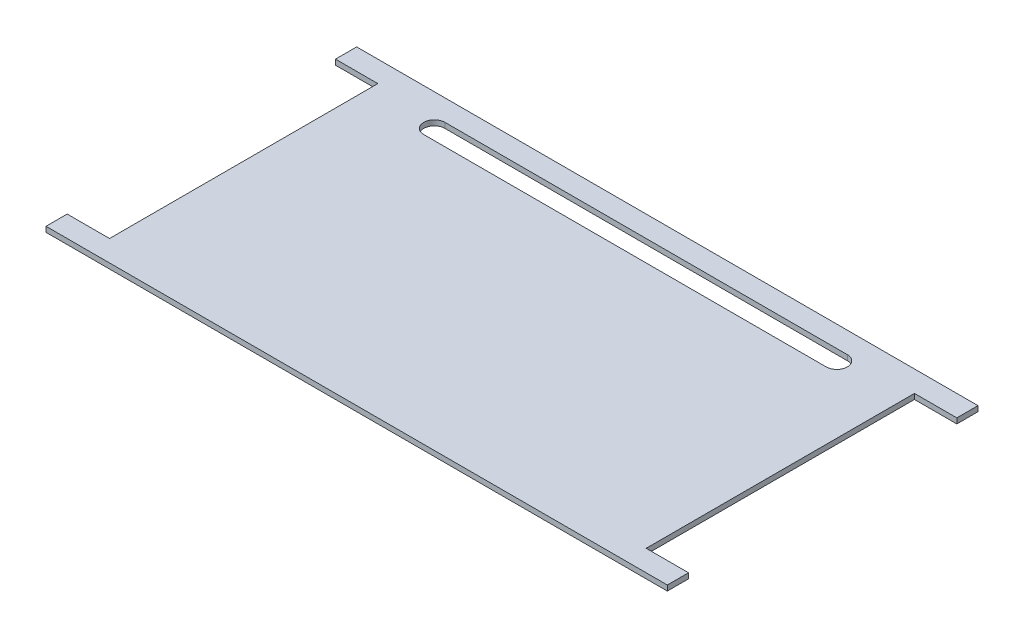
SolidWorks part; units mm, degrees
material "Maple"
ref_plane "Front Plane" through (0, 0, 0) normal (0, 0, 1) x (1, 0, 0)
ref_plane "Top Plane" through (0, 0, 0) normal (0, 1, 0) x (1, 0, 0)
ref_plane "Right Plane" through (0, 0, 0) normal (1, 0, 0) x (0, 0, -1)
sketch "Sketch1" plane through (0, 0, 0) normal (0, 1, 0) x (1, 0, 0)
  line L1 (-279.4, -139.7) -> (279.4, -139.7)
  line L2 (-279.4, -139.7) -> (-279.4, 139.7)
  line L3 (-279.4, 139.7) -> (279.4, 139.7)
  line L4 (279.4, -139.7) -> (279.4, 139.7)
  line L5 (-279.4, -139.7) -> (279.4, 139.7) construction
  line L6 (-279.4, 139.7) -> (279.4, -139.7) construction
  point P0 (0, 0)
  dimension "D1" = 279.4
  dimension "D2" = 558.8
extrude "Boss-Extrude1" add sketch "Sketch1" along normal mid plane 4.7625 contours L3 L4 L1 L2
sketch "Sketch2" plane through (0, 2.3813, 0) normal (0, 1, 0) x (1, 0, 0)
  line L0 (-279.4, -139.7) -> (-279.4, 139.7) construction
  line L1 (-279.4, 120.65) -> (-241.3, 120.65)
  line L2 (-279.4, 120.65) -> (-279.4, -120.65)
  line L3 (-279.4, -120.65) -> (-241.3, -120.65)
  line L4 (-241.3, 120.65) -> (-241.3, -120.65)
  line L5 (279.4, -139.7) -> (279.4, 139.7) construction
  line L6 (279.4, 120.65) -> (241.3, 120.65)
  line L7 (279.4, 120.65) -> (279.4, -120.65)
  line L8 (279.4, -120.65) -> (241.3, -120.65)
  line L9 (241.3, 120.65) -> (241.3, -120.65)
  line L10 (-241.3, 0) -> (241.3, 0) construction
  line L11 (-279.4, -139.7) -> (279.4, -139.7) construction
  dimension "D1" = 38.1
  dimension "D2" = 19.05
extrude "Cut-Extrude1" cut sketch "Sketch2" against normal through all
sketch "Sketch3" plane through (0, 2.3813, 0) normal (0, 1, 0) x (1, 0, 0)
  line L0 (-279.4, 139.7) -> (279.4, 139.7) construction
  line L1 (-190.5, 139.7) -> (190.5, 139.7)
  line L2 (-190.5, 139.7) -> (-190.5, 114.3)
  line L3 (-190.5, 114.3) -> (190.5, 114.3)
  line L4 (190.5, 139.7) -> (190.5, 114.3)
  line L5 (0, 0) -> (0, 114.3) construction
  line L6 (-241.3, -120.65) -> (-241.3, 120.65) construction
  dimension "D1" = 50.8
  dimension "D2" = 25.4
extrude "Cut-Extrude2" [suppressed] cut sketch "Sketch3" against normal through all
sketch "Sketch4" plane through (0, 2.3813, 0) normal (0, 1, 0) x (1, 0, 0)
  line L0 (-180.975, 111.125) -> (180.975, 111.125) construction
  line L1 (-180.975, 120.65) -> (180.975, 120.65)
  line L2 (-180.975, 101.6) -> (180.975, 101.6)
  line L6 (-241.3, -120.65) -> (-241.3, 120.65) construction
  line L7 (0, 111.125) -> (0, 0) construction
  line L8 (-279.4, 139.7) -> (279.4, 139.7) construction
  arc A0 (-180.975, 120.65) -> (-180.975, 101.6) centre (-180.975, 111.125) ccw
  arc A1 (180.975, 101.6) -> (180.975, 120.65) centre (180.975, 111.125) ccw
  point P2 (0, 111.125)
  dimension "D1" = 50.8
  dimension "D2" = 19.05
  dimension "D3" = 19.05
extrude "Cut-Extrude3" cut sketch "Sketch4" against normal through all
